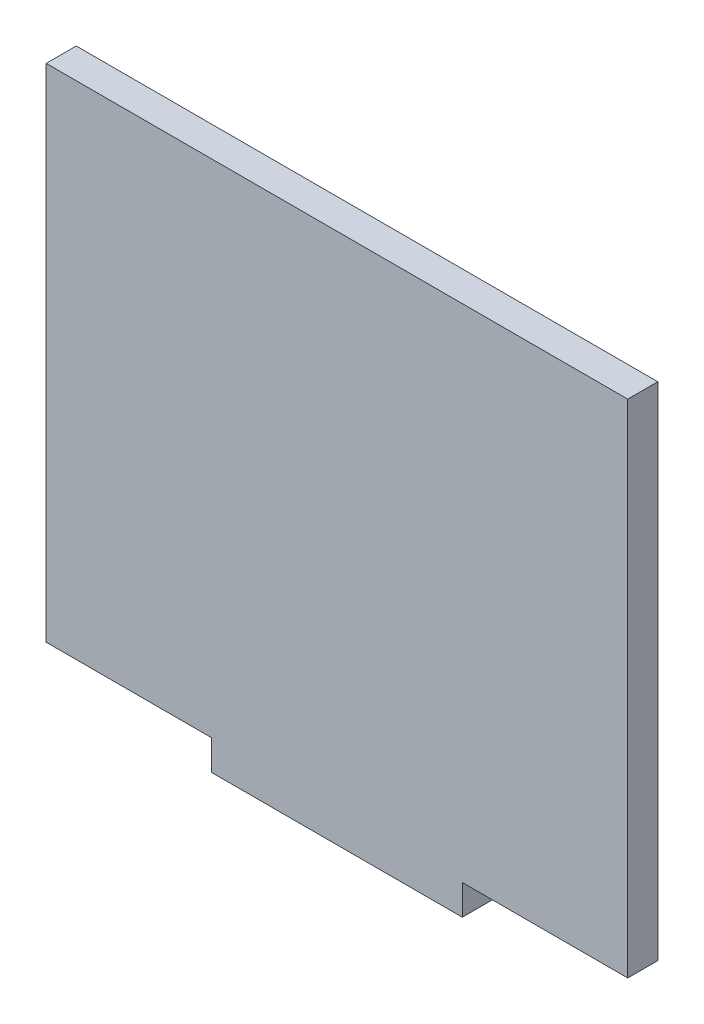
SolidWorks part; units mm, degrees
material "Maple"
ref_plane "Front Plane" through (0, 0, 0) normal (0, 0, 1) x (1, 0, 0)
ref_plane "Top Plane" through (0, 0, 0) normal (0, 1, 0) x (1, 0, 0)
ref_plane "Right Plane" through (0, 0, 0) normal (1, 0, 0) x (0, 0, -1)
sketch "Sketch1" plane through (0, 0, 0) normal (0, 0, 1) x (1, 0, 0)
  line L0 (-41, 125) -> (-41, 25)
  line L1 (-41, 125) -> (75, 125)
  line L3 (-41, 25) -> (-8, 25)
  line L5 (75, 125) -> (75, 25)
  line L6 (42, 25) -> (75, 25)
  line L17 (-8, 25) -> (-8, 19)
  line L18 (-8, 19) -> (42, 19)
  line L19 (42, 25) -> (42, 19)
  point P0 (0, 0)
  point P6 (0, -125)
  dimension "D1" = 116
  dimension "D2" = 100
  dimension "D3" = 50
  dimension "D4" = 33
  dimension "D5" = 33
  dimension "D6" = 6
extrude "Boss-Extrude1" add sketch "Sketch1" along normal blind 6
